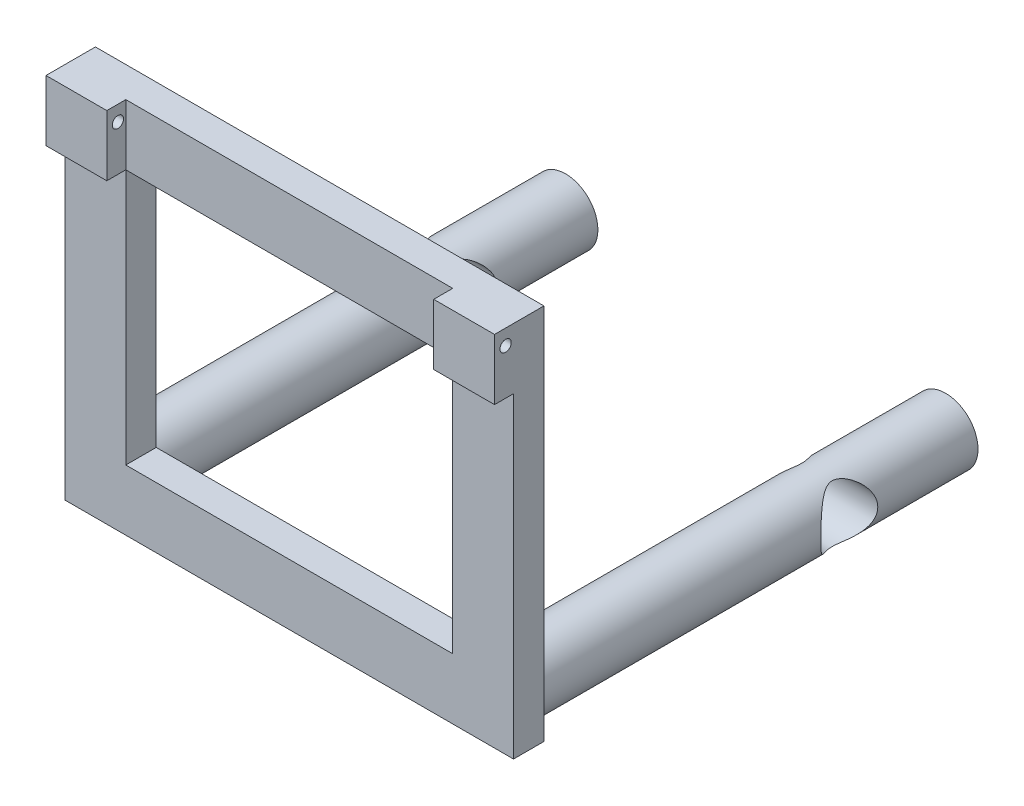
SolidWorks part; units mm, degrees
ref_plane "Front Plane" through (0, 0, 0) normal (0, 0, 1) x (1, 0, 0)
ref_plane "Top Plane" through (0, 0, 0) normal (0, 1, 0) x (1, 0, 0)
ref_plane "Right Plane" through (0, 0, 0) normal (1, 0, 0) x (0, 0, -1)
sketch "Sketch1" plane through (0, 0, 0) normal (0, 0, 1) x (1, 0, 0)
  line L0 (-796.3832, -7.0403) -> (-796.3832, -679.6151)
  line L1 (-956.3832, 152.9597) -> (223.6879, 152.9597)
  line L2 (-956.3832, 152.9597) -> (-956.3832, -839.6151)
  line L3 (-956.3832, -839.6151) -> (223.6879, -839.6151)
  line L4 (223.6879, 152.9597) -> (223.6879, -839.6151)
  line L9 (-796.3832, -679.6151) -> (63.6879, -679.6151)
  line L10 (63.6879, -7.0403) -> (63.6879, -679.6151)
  line L11 (-796.3832, -7.0403) -> (63.6879, -7.0403)
  point P8 (-603.3444, -570.2499)
  point P9 (-653.3655, -665.5411)
  point P10 (-956.3832, -839.6151)
  dimension "D1" = 160
extrude "Boss-Extrude2" add sketch "Sketch1" along normal blind 80
sketch "Sketch2" plane through (0, 0, 80) normal (0, 0, 1) x (1, 0, 0)
  line L1 (-956.3832, 152.9597) -> (-796.3832, 152.9597)
  line L2 (-956.3832, 152.9597) -> (-956.3832, -7.0403)
  line L3 (-956.3832, -7.0403) -> (-796.3832, -7.0403)
  line L4 (-796.3832, 152.9597) -> (-796.3832, -7.0403)
  line L5 (63.6879, -7.0403) -> (223.6879, -7.0403)
  line L6 (63.6879, -7.0403) -> (63.6879, 152.9597)
  line L7 (63.6879, 152.9597) -> (223.6879, 152.9597)
  line L8 (223.6879, -7.0403) -> (223.6879, 152.9597)
extrude "Boss-Extrude3" add sketch "Sketch2" along normal blind 50
sketch "Sketch3" plane through (223.6879, 0, 0) normal (1, 0, 0) x (0, 0, -1)
  circle A0 centre (-100.8438, 112.4049) radius 14.8547
  point P2 (-100.8438, 112.4049)
extrude "Cut-Extrude1" cut sketch "Sketch3" against normal through all and the other way through all
sketch "Sketch4" plane through (0, 0, 0) normal (0, 0, -1) x (-1, 0, 0)
  line L0 (956.3832, 152.9597) -> (956.3832, -839.6151) construction
  line L1 (-223.6879, -839.6151) -> (-223.6879, 152.9597) construction
  line L2 (956.3832, -839.6151) -> (-223.6879, -839.6151) construction
  circle A1 centre (-133.6879, -749.6151) radius 85
  circle A2 centre (866.3832, -749.6151) radius 85
  point P9 (862.8945, -749.6151)
  dimension "D1" = 170
  dimension "D4" = 170
  dimension "D5" = 90
  dimension "D2" = 90
  dimension "D3" = 90
  dimension "D6" = 90
extrude "Boss-Extrude4" add sketch "Sketch4" along normal blind 1147
ref_plane "Plane1" through (233.6879, 0, 0) normal (1, 0, 0) x (0, 0, -1)
sketch "Sketch5" plane through (233.6879, 0, 0) normal (1, 0, 0) x (0, 0, -1)
  line L1 (0, -834.6151) -> (1147, -834.6151) construction
  circle A0 centre (808.3432, -749.6151) radius 75
  point P2 (808.3432, -747.3336)
  dimension "D1" = 150
  dimension "D2" = 85
extrude "Cut-Extrude2" cut sketch "Sketch5" against normal through all
